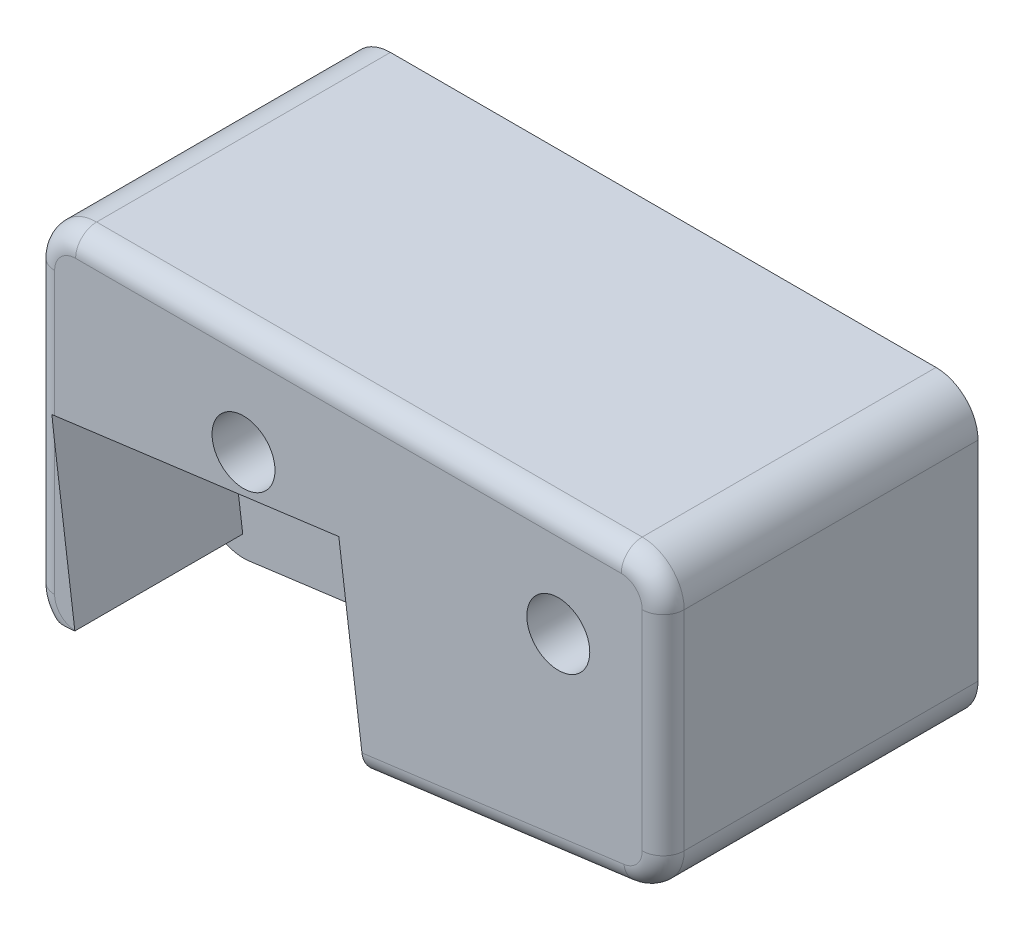
SolidWorks part; units mm, degrees
ref_plane "Front Plane" through (0, 0, 0) normal (0, 0, 1) x (1, 0, 0)
ref_plane "Top Plane" through (0, 0, 0) normal (0, 1, 0) x (1, 0, 0)
ref_plane "Right Plane" through (0, 0, 0) normal (1, 0, 0) x (0, 0, -1)
sketch "Sketch1" plane through (0, 0, 0) normal (0, 0, 1) x (1, 0, 0)
  line L1 (0, 0) -> (30, 0)
  line L2 (0, 0) -> (0, 10)
  line L3 (0, 10) -> (30, 10)
  line L4 (30, 0) -> (30, 10)
  line L7 (10, 5) -> (25, 5) construction
  circle A0 centre (10, 5) radius 1.5
  circle A3 centre (25, 5) radius 1.5
  dimension "D1" = 10
  dimension "D3" = 3
  dimension "D2" = 30
  dimension "D4" = 10
  dimension "D5" = 5
  dimension "D6" = 5
extrude "Boss-Extrude1" add sketch "Sketch1" along normal blind 15
sketch "Sketch2" plane through (0, 0, 15) normal (0, 0, 1) x (1, 0, 0)
  line L1 (30, 0) -> (0, 0)
  line L2 (30, 0) -> (30, -3.7049)
  line L3 (30, -3.7049) -> (0, -7.6545)
  line L4 (0, -7.6545) -> (0, 0)
  line L5 (30, -3.7049) -> (0, -3.7049) construction
  circle A0 centre (10, 5) radius 1.5 construction
  dimension "D2" = 12.6545
  dimension "D1" = 7.5
extrude "Boss-Extrude3" add sketch "Sketch2" against normal through all
sketch "Sketch3" plane through (0, 0, 15) normal (0, 0, 1) x (1, 0, 0)
  line L4 (5, -1.5) -> (11.5, -0.6443) construction
  line L5 (0, -7.6545) -> (30, -3.7049) construction
  line L6 (0, -7.6545) -> (30, -3.7049) construction
  circle A0 centre (10, 5) radius 1.5 construction
  circle A2 centre (5, -1.5) radius 1.1
  circle A3 centre (11.5, -0.6443) radius 1.1
  point P5 (3.8972, -2.6816)
  point P11 (0, 0)
  dimension "D1" = 2.2
  dimension "D3" = 6.5
  dimension "D4" = 5
  dimension "D2" = 6.5
extrude "Cut-Extrude1" cut sketch "Sketch3" against normal through all
sketch "Sketch4" plane through (0, 0, 15) normal (0, 0, 1) x (1, 0, 0)
  line L0 (1.9631, -6.396) -> (0.8591, 1.9894)
  line L1 (0, -7.6545) -> (30, -3.7049) construction
  line L2 (0.8591, 1.9894) -> (14.5411, 3.7906)
  line L3 (14.5411, 3.7906) -> (15.7744, -5.5777)
  line L4 (15.7744, -5.5777) -> (0, -7.6545)
  line L5 (15.2201, -5.1976) -> (14.7371, -1.5293) construction
  line L6 (2.0466, -3.2) -> (2.5296, -6.8684) construction
  line L7 (2.2827, 1.6725) -> (3.175, 1.7899) construction
  line L8 (0, -7.6545) -> (0, -6.6545)
  line L9 (0, 10) -> (0, -7.6545) construction
  line L10 (0, -6.6545) -> (1.9631, -6.396)
  point P17 (0.062, -7.6463)
  dimension "D1" = 0.5
  dimension "D2" = 0.5
  dimension "D3" = 0.5
  dimension "D4" = 1
extrude "Cut-Extrude2" cut sketch "Sketch4" against normal offset from surface (8 mm away) 7 up to face at (6.1, -1.5, 0)
fillet "Fillet1" radius 2 4 edges at (30, 10, 7.5) (0, 10, 7.5) (0, -7.6545, 3.5) (30, -3.7049, 7.5)
fillet "Fillet2" radius 1 8 edges at (22.0177, -4.7558, 15) (29.5037, -3.2696, 15) (30, 3.0245, 15) (29.4142, 9.4142, 15) (0.1077, -6.0215, 15) (0, 1.313, 15) (0.5858, 9.4142, 15) (15, 10, 15)
